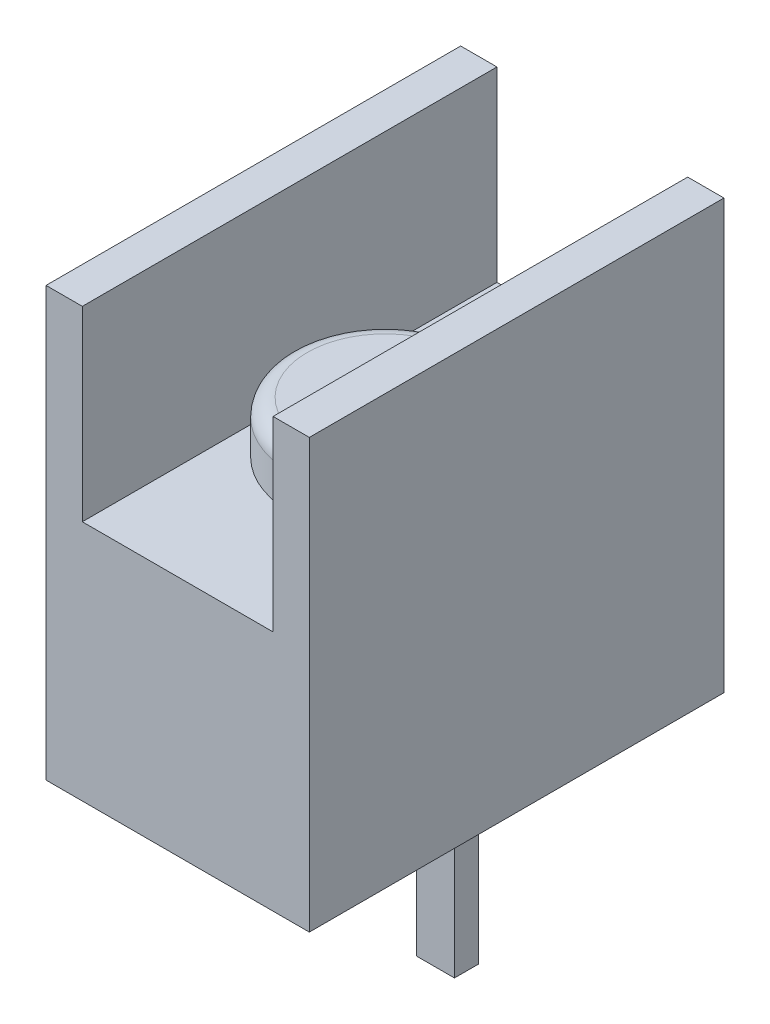
SolidWorks part; units mm, degrees
ref_plane "前视基准面" through (0, 0, 0) normal (0, 0, 1) x (1, 0, 0)
ref_plane "上视基准面" through (0, 0, 0) normal (0, 1, 0) x (1, 0, 0)
ref_plane "右视基准面" through (0, 0, 0) normal (1, 0, 0) x (0, 0, -1)
sketch "草图1" plane through (0, 0, 0) normal (0, 1, 0) x (1, 0, 0)
  line L0 (-11.1447, 0) -> (12.1543, 0) construction
  line L1 (-3.81, 6) -> (3.81, 6)
  line L2 (-3.81, 6) -> (-3.81, -6)
  line L3 (-3.81, -6) -> (3.81, -6)
  line L4 (3.81, 6) -> (3.81, -6)
  line L5 (0, 11.4931) -> (0, -8.9219) construction
  dimension "D1" = 7.62
  dimension "D2" = 12
extrude "拉伸1" add sketch "草图1" along normal blind 12.4
sketch "草图2" plane through (0, 12.4, 0) normal (0, 1, 0) x (-1, 0, 0)
  line L0 (3.81, 6) -> (-3.81, 6) construction
  line L1 (-2.76, 6) -> (2.76, 6)
  line L3 (-2.76, 6) -> (-2.76, -6)
  line L4 (-2.76, -6) -> (2.76, -6)
  line L5 (2.76, 6) -> (2.76, -6)
  line L6 (-3.81, -6) -> (3.81, -6) construction
  line L7 (-3.81, 6) -> (-3.81, -6) construction
  line L10 (3.81, -6) -> (3.81, 6) construction
  dimension "D1" = 1.05
  dimension "D2" = 1.05
extrude "切除-拉伸1" cut sketch "草图2" against normal offset from surface (5.4 mm away) 7 up to face at (0, 0, 0)
sketch "草图3" plane through (0, 0, 0) normal (0, -1, 0) x (1, 0, 0)
  line L0 (-1.1261, 0) -> (1.1036, 0) construction
  line L1 (1.26, 0.35) -> (2.36, 0.35)
  line L2 (1.26, 0.35) -> (1.26, -0.35)
  line L3 (1.26, -0.35) -> (2.36, -0.35)
  line L4 (2.36, 0.35) -> (2.36, -0.35)
  line L5 (1.81, 0.8666) -> (1.81, -0.8367) construction
  line L6 (3.81, 6) -> (3.81, -6) construction
  dimension "D2" = 0.7
  dimension "D1" = 1.1
  dimension "D3" = 2
extrude "拉伸2" add sketch "草图3" along normal blind 4.7
sketch "草图4" plane through (0, 7, 0) normal (0, 1, 0) x (-1, 0, 0)
  line L0 (-9.5136, 0) -> (8.6579, 0) construction
  line L1 (0, -7.7686) -> (0, 8.3952) construction
  circle A1 centre (0, 0) radius 2.75
  dimension "D1" = 5.5
extrude "凸台-拉伸1" add sketch "草图4" along normal blind 1.5
fillet "圆角1" radius 0.5 1 edges at (0, 8.5, -2.75)
